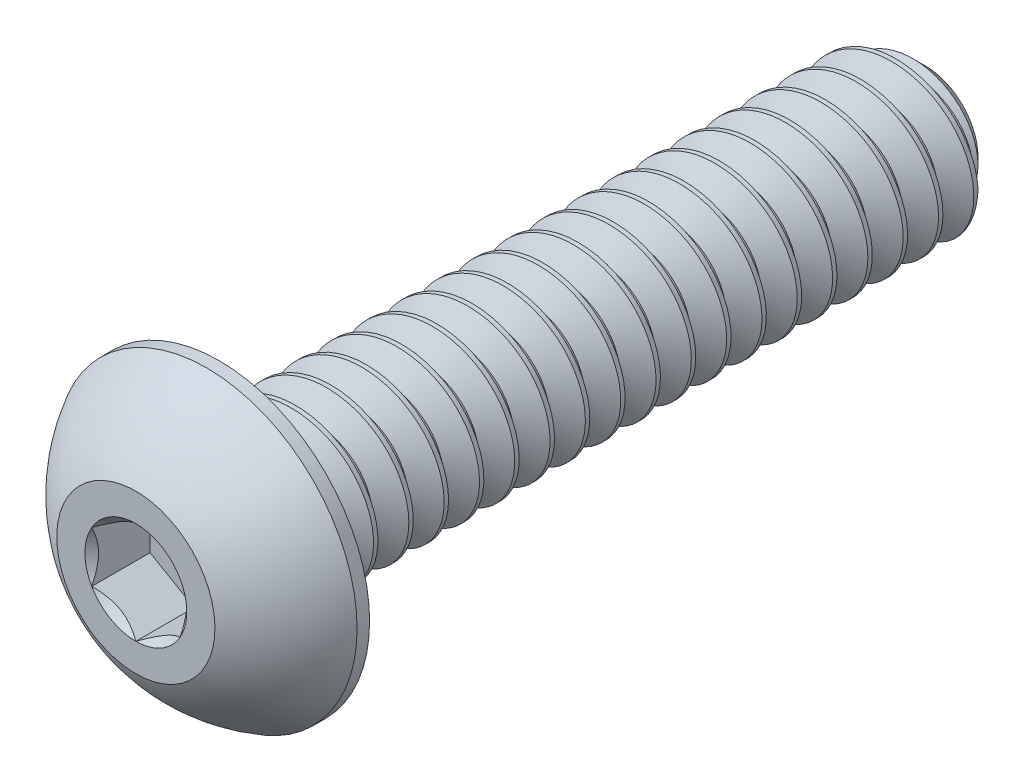
SolidWorks part; units mm, degrees
ref_plane "Front" through (0, 0, 0) normal (0, 0, 1) x (1, 0, 0)
ref_plane "Top" through (0, 0, 0) normal (0, 1, 0) x (1, 0, 0)
ref_plane "Right" through (0, 0, 0) normal (1, 0, 0) x (0, 0, -1)
sketch "Sketch1" plane through (0, 0, 0) normal (1, 0, 0) x (0, 0, -1)
  line L2 (1.4986, 1.4224) -> (14.1986, 1.4224)
  line L3 (14.1986, 1.4224) -> (14.1986, 0)
  line L4 (14.1986, 0) -> (1.4986, 0)
  line L6 (1.2738, 2.7051) -> (1.4986, 2.7051) construction
  line L7 (14.1986, 1.4224) -> (14.1986, -1.4224) construction
  line L8 (0, 0) -> (1.4986, 0) construction
  line L9 (1.4986, 2.7051) -> (1.4986, -2.7051) construction
  line L11 (1.4986, 1.4224) -> (1.4986, 0)
  line L13 (0, 0.7937) -> (0, -0.7937) construction
  line L14 (0, 0.7937) -> (0, 1.4224) construction
  arc A3 (0, 1.4224) -> (1.2738, 2.7051) centre (2.7151, 0) cw construction
  dimension "D1" = 0.2248
  dimension "Head Ht" = 1.4986
  dimension "Head Dia" = 5.4102
  dimension "Dia" = 2.8448
  dimension "Lg" = 12.7
  dimension "Hex" = 1.5875
revolve "Revolve1" add sketch "Sketch1" angle 360 mid plane about L4
sketch "Sketch3" plane through (0, 0, -14.1986) normal (0, 0, -1) x (-1, 0, 0)
  circle A0 centre (0, 0) radius 1.4224
curve "Helix/Spiral1" pitch 0.635 height 13.335 radius 1.4224 centre (0, 0, -14.1986) axis (0, 0, 1) start towards (0, 1, 0)
sketch "Sketch2" plane through (0, 0, 0) normal (1, 0, 0) x (0, 0, -1)
  line L0 (14.1986, 1.4224) -> (14.7542, 1.4224)
  line L1 (14.7542, 1.4224) -> (14.5161, 1.01)
  line L2 (14.5161, 1.01) -> (14.4367, 1.01)
  line L3 (14.4367, 1.01) -> (14.1986, 1.4224)
  line L4 (14.3177, 1.2162) -> (14.6352, 1.2162) construction
  dimension "D1" = 60
  dimension "D2" = 0.0794
  dimension "D3" = 0.3175
chamfer "Chamfer1" distance 0.4763 angle 45 1 edges at (0, 1.4224, -14.1986)
sweep "Cut-Sweep1" cut profiles "Sketch2" path "Helix/Spiral1" align with end faces yes
sketch "Sketch7" plane through (0, 0, 0) normal (1, 0, 0) x (0, 0, -1)
  line L6 (1.2738, 2.7051) -> (1.4986, 2.7051) construction
  line L8 (0, 0) -> (1.4986, 0) construction
  line L11 (1.4986, 2.7051) -> (1.4986, -2.7051) construction
  line L12 (1.2738, 2.7051) -> (1.4986, 2.7051)
  line L13 (0, 0) -> (1.4986, 0)
  line L14 (0, 0.7937) -> (0, -0.7937) construction
  line L15 (1.4986, 2.7051) -> (1.4986, 0)
  line L16 (0, 1.4224) -> (0, 0)
  arc A2 (1.2738, 2.7051) -> (0, 1.4224) centre (2.7151, 0) ccw construction
  arc A3 (1.2738, 2.7051) -> (0, 1.4224) centre (2.7151, 0) ccw
revolve "Revolve2" add sketch "Sketch7" angle 360 mid plane about L13
sketch "Sketch5" plane through (0, 0, 0) normal (0, 0, 1) x (1, 0, 0)
  line L1 (0.7937, -0.4583) -> (0.7937, 0.4583)
  line L2 (0.7937, 0.4583) -> (0, 0.9165)
  line L3 (0, 0.9165) -> (-0.7937, 0.4583)
  line L4 (-0.7937, 0.4583) -> (-0.7937, -0.4583)
  line L5 (-0.7937, -0.4583) -> (0, -0.9165)
  line L6 (0, -0.9165) -> (0.7937, -0.4583)
  circle A0 centre (0, 0) radius 0.7937 construction
extrude "Cut-Extrude2" cut sketch "Sketch5" against normal blind 1.049
sketch "Sketch6" plane through (0, 0, 0) normal (0, 0, 1) x (1, 0, 0)
  circle A0 centre (0, 0) radius 0.9165
extrude "Cut-Extrude3" cut sketch "Sketch6" against normal blind 1.049 draft 45
sketch "Sketch9" [suppressed] plane through (0, 0, -1.4986) normal (0, 0, 1) x (1, 0, 0)
  circle A2 centre (0, 0) radius 1.4224
extrude "Boss-Extrude2" [suppressed] add sketch "Sketch9" against normal offset from surface (6.35 mm away) 28.575 up to face at (0, 0.9462, -14.1986)
sketch "Sketch10" plane through (0, 0, 0) normal (1, 0, 0) x (0, 0, -1)
  line L0 (14.1986, 1.4224) -> (14.1986, -1.4224) construction
  point P0 (13.2461, -1.4224)
  dimension "D1" = 0.9525
equation "\"D3@Helix/Spiral1\" = \"Lg@Sketch1\" + \"D4@Helix/Spiral1\""
equation "\"D2@Sketch2\" = \"D4@Helix/Spiral1\" * .125"
equation "\"D3@Sketch2\" = \"D4@Helix/Spiral1\" * .5"
equation "\"D1@Chamfer1\" = \"D4@Helix/Spiral1\" * .75"
equation "\"D1@Cut-Extrude2\" = \"Head Ht@Sketch1\" * .7"
equation "\"D1@Sketch1\" = \"Head Ht@Sketch1\" * .15"
equation "\"D1@Sketch10\" = \"D4@Helix/Spiral1\" * 1.5"
equation "\"D1@Cut-Extrude3\" = \"D1@Cut-Extrude2\""
